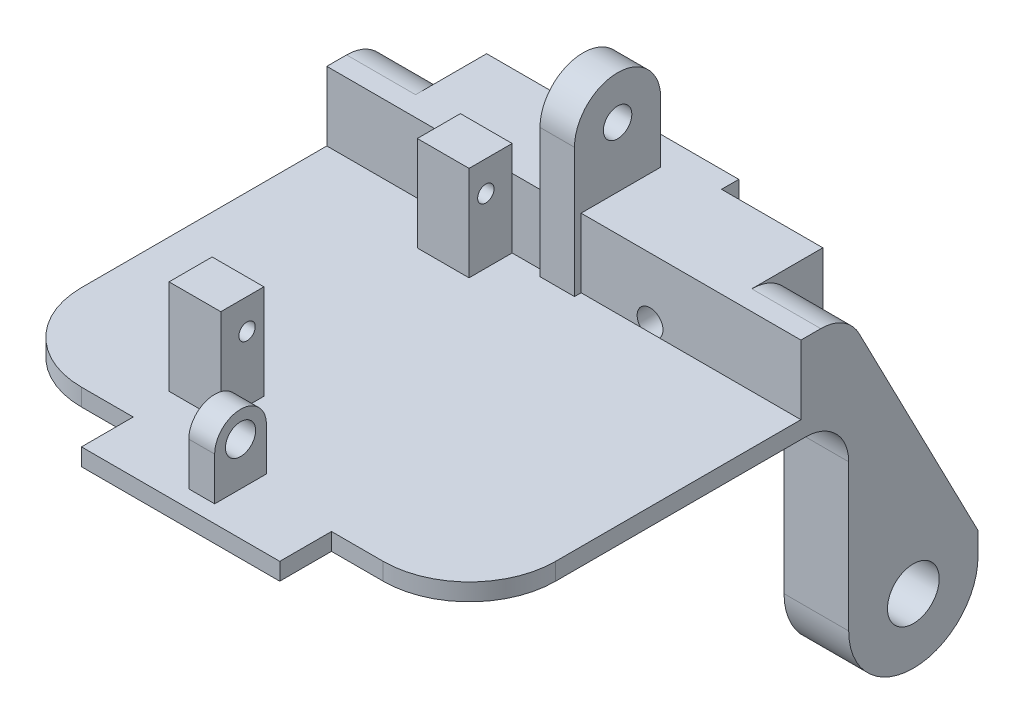
SolidWorks part; units mm, degrees
ref_plane "前视基准面" through (0, 0, 0) normal (0, 0, 1) x (1, 0, 0)
ref_plane "上视基准面" through (0, 0, 0) normal (0, 1, 0) x (1, 0, 0)
ref_plane "右视基准面" through (0, 0, 0) normal (1, 0, 0) x (0, 0, -1)
sketch "草图1" plane through (0, 0, 0) normal (0, 1, 0) x (1, 0, 0)
  line L1 (-27.5, -19.5) -> (27.5, -19.5)
  line L2 (-27.5, -19.5) -> (-27.5, 19.5)
  line L3 (-27.5, 19.5) -> (27.5, 19.5)
  line L4 (27.5, -19.5) -> (27.5, 19.5)
  line L5 (-27.5, -19.5) -> (27.5, 19.5) construction
  line L6 (-27.5, 19.5) -> (27.5, -19.5) construction
  point P0 (0, 0)
  dimension "D1" = 55
  dimension "D2" = 39
extrude "凸台-拉伸1" add sketch "草图1" along normal blind 2
sketch "草图2" plane through (0, 2, 0) normal (0, 1, 0) x (1, 0, 0)
  line L0 (-27.5, -19.5) -> (27.5, -19.5) construction
  line L1 (-11.5, -19.5) -> (11.5, -19.5)
  line L2 (-11.5, -19.5) -> (-11.5, -25.5)
  line L3 (-11.5, -25.5) -> (11.5, -25.5)
  line L4 (11.5, -19.5) -> (11.5, -25.5)
  line L5 (27.5, 19.5) -> (-27.5, 19.5) construction
  point P9 (0, -25.5)
  dimension "D1" = 23
  dimension "D2" = 45
extrude "凸台-拉伸2" add sketch "草图2" against normal blind 2
sketch "草图3" plane through (0, 2, 0) normal (0, 1, 0) x (1, 0, 0)
  line L1 (-6, -14.8415) -> (-12, -14.8415)
  line L2 (-6, -14.8415) -> (-6, -9.8415)
  line L3 (-6, -9.8415) -> (-12, -9.8415)
  line L4 (-12, -14.8415) -> (-12, -9.8415)
  line L6 (-6, 13.9585) -> (-12, 13.9585)
  line L7 (-6, 13.9585) -> (-6, 18.9585)
  line L8 (-6, 18.9585) -> (-12, 18.9585)
  line L9 (-12, 13.9585) -> (-12, 18.9585)
  dimension "D1" = 6
  dimension "D2" = 23.8
  dimension "D3" = 6
  dimension "D4" = 6
  dimension "D5" = 6
  dimension "D6" = 5
  dimension "D7" = 5
extrude "凸台-拉伸3" add sketch "草图3" along normal blind 11
sketch "草图5" plane through (-12, 0, 0) normal (-1, 0, 0) x (0, 0, 1)
  line L0 (-13.9585, 13) -> (-13.9585, 2) construction
  line L1 (9.8415, 13) -> (9.8415, 2) construction
  line L2 (-19.5, 2) -> (19.5, 2) construction
  line L3 (9.8415, 2) -> (14.8415, 2) construction
  circle A0 centre (-15.9085, 9.5) radius 0.95
  circle A1 centre (11.7915, 9.5) radius 0.95
  dimension "D1" = 1.95
  dimension "D2" = 1.95
  dimension "D3" = 7.5
  dimension "D4" = 7.5
  dimension "D5" = 27.7
  dimension "D6" = 1.9
  dimension "D7" = 1.9
extrude "切除-拉伸1" cut sketch "草图5" against normal blind 11
sketch "草图6" plane through (0, 2, 0) normal (0, 1, 0) x (1, 0, 0)
  line L0 (27.5, -19.5) -> (27.5, 19.5) construction
  line L1 (-27.5, 19.5) -> (27.5, 19.5)
  line L2 (-27.5, 19.5) -> (-27.5, 18.9585)
  line L3 (-27.5, 18.9585) -> (27.5, 18.9585)
  line L4 (27.5, 19.5) -> (27.5, 18.9585)
  line L5 (-6, 18.9585) -> (-12, 18.9585) construction
extrude "凸台-拉伸4" add sketch "草图6" along normal blind 8
sketch "草图8" plane through (0, 0, 0) normal (1, 0, 0) x (0, 0, -1)
  line L0 (28.1899, 17) -> (28.1899, 0)
  line L1 (-19.5, 2) -> (18.9585, 2) construction
  line L2 (18.1899, 17) -> (18.1899, 0)
  line L4 (18.1899, 0) -> (28.1899, 0)
  line L7 (-19.5, 0) -> (19.5, 0) construction
  arc A0 (28.1899, 17) -> (18.1899, 17) centre (23.1899, 17) ccw
  circle A1 centre (23.1899, 17) radius 1.65
  dimension "D1" = 15
  dimension "D2" = 10
  dimension "D3" = 3.3
extrude "凸台-拉伸6" add sketch "草图8" along normal mid plane 4
sketch "草图10" plane through (0, 2, 0) normal (0, 1, 0) x (1, 0, 0)
  line L0 (-11.5, -25.5) -> (11.5, -25.5) construction
  line L1 (-1.05, -17.5) -> (1.95, -17.5)
  line L2 (-1.05, -17.5) -> (-1.05, -23.5)
  line L3 (-1.05, -23.5) -> (1.95, -23.5)
  line L4 (1.95, -17.5) -> (1.95, -23.5)
  line L5 (11.5, -25.5) -> (11.5, -19.5) construction
  dimension "D1" = 2
  dimension "D2" = 3
  dimension "D3" = 6
  dimension "D4" = 9.55
extrude "凸台-拉伸7" add sketch "草图10" along normal blind 8
sketch "草图11" plane through (0, 0, -18.9585) normal (0, 0, 1) x (1, 0, 0)
  line L0 (-2, 10) -> (-27.5, 10) construction
  circle A0 centre (-10, 3) radius 1.5
  dimension "D1" = 10
  dimension "D2" = 3
  dimension "D3" = 7
extrude "切除-拉伸3" cut sketch "草图11" against normal blind 13
sketch "草图12" plane through (-27.5, 0, 0) normal (-1, 0, 0) x (0, 0, 1)
  line L1 (-19.5, 0) -> (4.0888, 0)
  line L2 (-19.5, 0) -> (19.5, 0) construction
  line L3 (-19.5, 10) -> (-19.5, 0) construction
  line L4 (-39.5, -22) -> (-39.5, 10)
  line L5 (-19.5, 10) -> (-39.5, 10)
  line L6 (-24.5, -22) -> (-24.5, 0)
  line L7 (-24.5, 0) -> (-19.5, 0)
  line L8 (-19.5, 10) -> (-19.5, 0)
  arc A0 (-39.5, -22) -> (-24.5, -22) centre (-32, -22) ccw
  circle A2 centre (-32, -22) radius 3
  line M7 (-19.5, 10) -> (-19.5, 0)
  dimension "D1" = 15
  dimension "D5" = 6
  dimension "D2" = 22
  dimension "D3" = 12.5
extrude "凸台-拉伸8" add sketch "草图12" against normal blind 7.5 contours L4 A0 L6 L7 L5 A2 M7 region at (-27.5, -7.1737, -31.1527)
sketch "草图13" plane through (0, 0, 0) normal (0, -1, 0) x (1, 0, 0)
  line L0 (-11.5, 25.5) -> (11.5, 25.5) construction
  line L1 (-5, 21) -> (5, 21)
  line L2 (-5, 21) -> (-5, 17.3)
  line L3 (-5, 17.3) -> (5, 17.3)
  line L4 (5, 21) -> (5, 17.3)
  line L5 (-5, 21) -> (5, 17.3) construction
  line L6 (-5, 17.3) -> (5, 21) construction
  point P0 (0, 19.15)
  dimension "D1" = 10
  dimension "D2" = 4.5
  dimension "D3" = 3.7
extrude "凸台-拉伸9" add sketch "草图13" along normal blind 1
mirror "镜向1" about plane through (0, 0, 0) normal (1, 0, 0) of "凸台-拉伸8", "切除-拉伸3"
fillet "圆角3" 2 edges at (0.45, 10, 17.5) (0.45, 10, 23.5) type full round first side face at (0.45, 6, 17.5) second side face at (0.45, 6, 23.5) middle face at (0.45, 10, 20.5)
sketch "草图15" plane through (-1.05, 0, 0) normal (-1, 0, 0) x (0, 0, 1)
  circle A0 centre (20.5, 7) radius 1.75
  dimension "D1" = 3.5
extrude "切除-拉伸5" cut sketch "草图15" against normal blind 23
sketch "草图16" plane through (0, 0, -19.5) normal (0, 0, -1) x (-1, 0, 0)
  line L0 (-20, 10) -> (-2, 10) construction
  line L1 (-7.75, 10) -> (7.75, 10)
  line L2 (-7.75, 10) -> (-7.75, 6)
  line L3 (-7.75, 6) -> (7.75, 6)
  line L4 (7.75, 10) -> (7.75, 6)
  point P6 (0, 6)
  dimension "D1" = 15.5
  dimension "D2" = 4
extrude "凸台-拉伸10" add sketch "草图16" along normal blind 20
sketch "草图17" plane through (0, 0, -19.5) normal (0, 0, -1) x (-1, 0, 0)
  line L6 (-20, 0) -> (-2, 0)
  line L7 (-20, 0) -> (-2, 0)
  line L8 (-20, 10) -> (-20, 0)
  line L10 (-7.75, 6) -> (-7.75, 10)
  line L11 (-7.75, 10) -> (-20, 10)
  line L12 (-2, 0) -> (-2, 6)
  line L14 (-2, 0) -> (-2, 6)
  line L15 (-7.75, 6) -> (-7.75, 10)
  line L16 (-2, 6) -> (-7.75, 6)
  line L18 (-2, 6) -> (-7.75, 6)
  line L21 (-7.75, 10) -> (-20, 10)
  line L32 (-20, 10) -> (-20, 0)
  line L33 (7.75, 6) -> (2, 6)
  line L34 (2, 6) -> (2, 0)
  line L35 (2, 0) -> (20, 0)
  line L36 (20, 0) -> (20, 10)
  line L37 (20, 10) -> (7.75, 10)
  line L38 (7.75, 10) -> (7.75, 6)
  line L39 (7.75, 6) -> (2, 6)
  line L40 (2, 6) -> (2, 0)
  line L41 (2, 0) -> (20, 0)
  line L42 (20, 0) -> (20, 10)
  line L43 (20, 10) -> (7.75, 10)
  line L44 (7.75, 10) -> (7.75, 6)
  circle A0 centre (10, 3) radius 1.5 construction
  circle A1 centre (-10, 3) radius 1.5 construction
  circle A2 centre (10, 3) radius 1.5
  circle A3 centre (-10, 3) radius 1.5
  dimension "D1" = 0
  dimension "D2" = 0
extrude "凸台-拉伸11" add sketch "草图17" along normal blind 10
fillet "圆角4" radius 10 2 edges at (23.75, 10, -39.5) (-23.75, 10, -39.5)
sketch "草图18" plane through (0, 10, 0) normal (0, 1, 0) x (1, 0, 0)
  line L0 (-7.75, 39.5) -> (7.75, 39.5) construction
  line L1 (-14.1233, 41.9545) -> (12.4415, 41.9545)
  line L2 (-14.1233, 41.9545) -> (-14.1233, 31.5)
  line L3 (-14.1233, 31.5) -> (12.4415, 31.5)
  line L4 (12.4415, 41.9545) -> (12.4415, 31.5)
  dimension "D1" = 8
extrude "切除-拉伸6" cut sketch "草图18" against normal blind 10
sketch "草图19" plane through (27.5, 0, 0) normal (1, 0, 0) x (0, 0, -1)
  line L0 (24.3, 10) -> (39.5, -19.3956)
  line L1 (39.5, -22) -> (39.5, 0) construction
  line L2 (24.3, 10) -> (39.5, 10)
  line L3 (39.5, 10) -> (39.5, -19.3956)
  dimension "D1" = 15.2
extrude "切除-拉伸7" cut sketch "草图19" against normal blind 8
sketch "草图20" plane through (-27.5, 0, 0) normal (-1, 0, 0) x (0, 0, 1)
  line L0 (-24.3, 10) -> (-39.5, 10)
  line L1 (-39.5, 10) -> (-39.5, -19.3956)
  line L8 (-39.5, -19.3956) -> (-39.5, -22)
  line L9 (-24.3, 10) -> (-39.5, -19.3956)
  line L10 (-18.9585, 10) -> (-24.3, 10)
  line L11 (-18.9585, 2) -> (-18.9585, 10)
  line L12 (19.5, 2) -> (-18.9585, 2)
  line L13 (19.5, 0) -> (19.5, 2)
  line L14 (-24.5, 0) -> (19.5, 0)
  line L15 (-24.5, -22) -> (-24.5, 0)
  line L17 (-24.3, 10) -> (-39.5, -19.3956)
  arc A1 (-39.5, -22) -> (-24.5, -22) centre (-32, -22) ccw
  dimension "D1" = 0
extrude "切除-拉伸8" cut sketch "草图20" against normal blind 8
fillet "圆角6" radius 5 4 edges at (23.75, 0, -24.5) (-23.75, 0, -24.5) (23.5, 10, -24.3) (-23.5, 10, -24.3)
sketch "草图21" plane through (0, -1, 0) normal (0, -1, 0) x (1, 0, 0)
  line L0 (-11.5, 25.5) -> (11.5, 25.5) construction
  line L1 (-27.5, -19.5) -> (-27.5, 19.5) construction
  circle A0 centre (0, 19.15) radius 1.4
  dimension "D1" = 2.8
  dimension "D2" = 6.35
  dimension "D3" = 27.5
extrude "切除-拉伸9" cut sketch "草图21" against normal blind 4
fillet "圆角7" radius 10 2 edges at (27.5, 1, 19.5) (-27.5, 1, 19.5)
